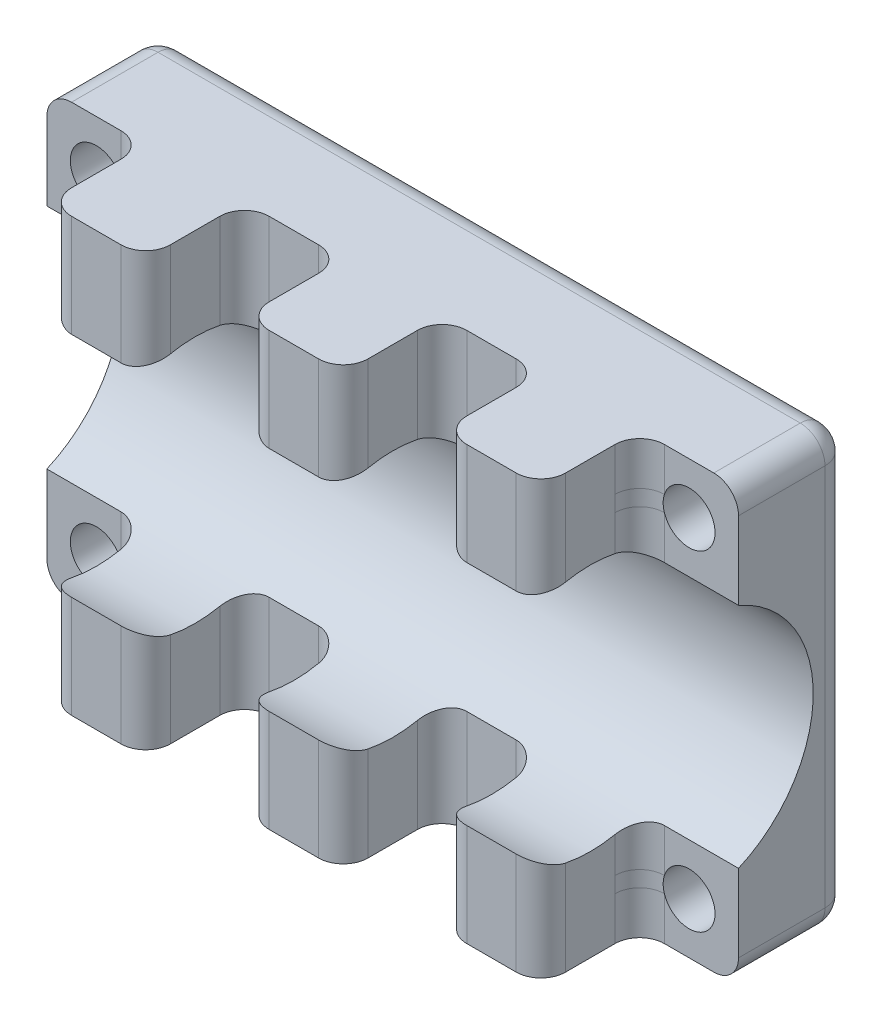
SolidWorks part; units mm, degrees
ref_plane "前视基准面" through (0, 0, 0) normal (0, 0, 1) x (1, 0, 0)
ref_plane "上视基准面" through (0, 0, 0) normal (0, 1, 0) x (1, 0, 0)
ref_plane "右视基准面" through (0, 0, 0) normal (1, 0, 0) x (0, 0, -1)
other "Configuration Table"
sketch "草图1" plane through (0, 0, 0) normal (0, 0, 1) x (1, 0, 0)
  line L1 (0, 0) -> (56, 0)
  line L2 (0, 0) -> (0, -35)
  line L3 (0, -35) -> (56, -35)
  line L4 (56, 0) -> (56, -35)
  dimension "D1" = 56
  dimension "D2" = 35
extrude "凸台-拉伸1" add sketch "草图1" along normal blind 26
sketch "草图2" plane through (56, 0, 0) normal (1, 0, 0) x (0, 0, -1)
  line L0 (-26, -17.5) -> (0, -17.5) construction
  line L1 (-26, -35) -> (-26, 0) construction
  line L2 (0, -35) -> (0, 0) construction
  line L3 (-13, 0) -> (-13, -35) construction
  line L4 (-26, 0) -> (0, 0) construction
  line L5 (-26, -35) -> (0, -35) construction
  circle A0 centre (-13, -17.5) radius 10.05
  dimension "D1" = 20.1
extrude "切除-拉伸1" cut sketch "草图2" against normal blind 73
sketch "草图3" plane through (0, 0, 0) normal (0, 1, 0) x (1, 0, 0)
  line L0 (28, 0) -> (28, -26) construction
  line L1 (0, -13) -> (56, -13) construction
  line L2 (0, -9) -> (8, -9)
  line L3 (8, -9) -> (8, -17)
  line L12 (56, 0) -> (0, 0)
  line L13 (0, 0) -> (0, -26)
  line L14 (0, -26) -> (56, -26)
  line L15 (56, -26) -> (56, 0)
  line L16 (56, 0) -> (0, 0)
  line L17 (0, 0) -> (0, -26)
  line L18 (0, -26) -> (56, -26)
  line L19 (56, -26) -> (56, 0)
  line L20 (8, -17) -> (16, -17)
  line L21 (16, -17) -> (16, -9)
  line L22 (16, -9) -> (24, -9)
  line L23 (24, -9) -> (24, -17)
  line L24 (24, -17) -> (32, -17)
  line L25 (32, -17) -> (32, -9)
  line L26 (32, -9) -> (40, -9)
  line L27 (40, -9) -> (40, -17)
  line L28 (40, -17) -> (48, -17)
  line L29 (48, -17) -> (48, -9)
  line L30 (48, -9) -> (56, -9)
  line M17 (0, 0) -> (0, -26)
  line M18 (0, -26) -> (56, -26)
  line M19 (56, -26) -> (56, 0)
  dimension "D2" = 9
  dimension "D3" = 8
  dimension "D4" = 8
  dimension "D5" = 8
  dimension "D1" = 0
extrude "切除-拉伸6" cut sketch "草图3" against normal blind 41 contours L30 L29 L28 L27 L26 L25 L24 L23 L22 L21 L20 L3 L2 M17 M18 M19 region at (28, 0, 18.6368)
sketch "草图6" plane through (0, 0, 0) normal (0, 0, -1) x (-1, 0, 0)
  line L0 (-48, -8.2803) -> (-56, -8.2803) construction
  line L1 (-56, -8.2803) -> (-56, 0) construction
  line L2 (-56, 0) -> (-48, 0) construction
  line L3 (-48, 0) -> (-48, -8.2803) construction
  line L4 (0, -8.2803) -> (-8, -8.2803) construction
  line L5 (-8, -8.2803) -> (-8, 0) construction
  line L6 (-8, 0) -> (0, 0) construction
  line L7 (0, 0) -> (0, -8.2803) construction
  line L8 (-48, -8.2803) -> (-56, -8.2803)
  line L9 (-56, -8.2803) -> (-56, 0)
  line L10 (-56, 0) -> (-48, 0)
  line L11 (-48, 0) -> (-48, -8.2803)
  line L12 (0, -8.2803) -> (-8, -8.2803)
  line L13 (-8, -8.2803) -> (-8, 0)
  line L14 (-8, 0) -> (0, 0)
  line L15 (0, 0) -> (0, -8.2803)
  line L16 (-56, -17.5) -> (0, -17.5) construction
  line L17 (-56, -35) -> (-56, 0) construction
  line L18 (0, 0) -> (0, -35) construction
  line L19 (-4, 0) -> (-4, -8.2803) construction
  line L20 (-52, 0) -> (-52, -8.2803) construction
  line L21 (-56, -4.1402) -> (0, -4.1402) construction
  circle A1 centre (-4, -4.1402) radius 2.1
  circle A2 centre (-52, -4.1402) radius 2.1
  circle A3 centre (-4, -30.8598) radius 2.1
  circle A4 centre (-52, -30.8598) radius 2.1
  dimension "D1" = 4.2
extrude "切除-拉伸7" cut sketch "草图6" against normal blind 41 contours A2 | A1 | A3 | A4
fillet "圆角3" radius 2 24 edges at (48, -4.1402, 9) (48, -4.1402, 17) (40, -4.1402, 17) (40, -4.1402, 9) (32, -4.1402, 17) (32, -4.1402, 9) (24, -4.1402, 17) (24, -4.1402, 9) (16, -4.1402, 17) (16, -4.1402, 9) (8, -4.1402, 17) (8, -4.1402, 9) (8, -30.8598, 9) (8, -30.8598, 17) (16, -30.8598, 17) (16, -30.8598, 9) (24, -30.8598, 9) (24, -30.8598, 17) (32, -30.8598, 17) (32, -30.8598, 9) (40, -30.8598, 9) (40, -30.8598, 17) (48, -30.8598, 17) (48, -30.8598, 9)
fillet "圆角4" radius 2 8 edges at (56, -35, 4.5) (56, 0, 4.5) (0, 0, 4.5) (0, -35, 4.5) (28, 0, 0) (0, -17.5, 0) (56, -17.5, 0) (28, -35, 0)
